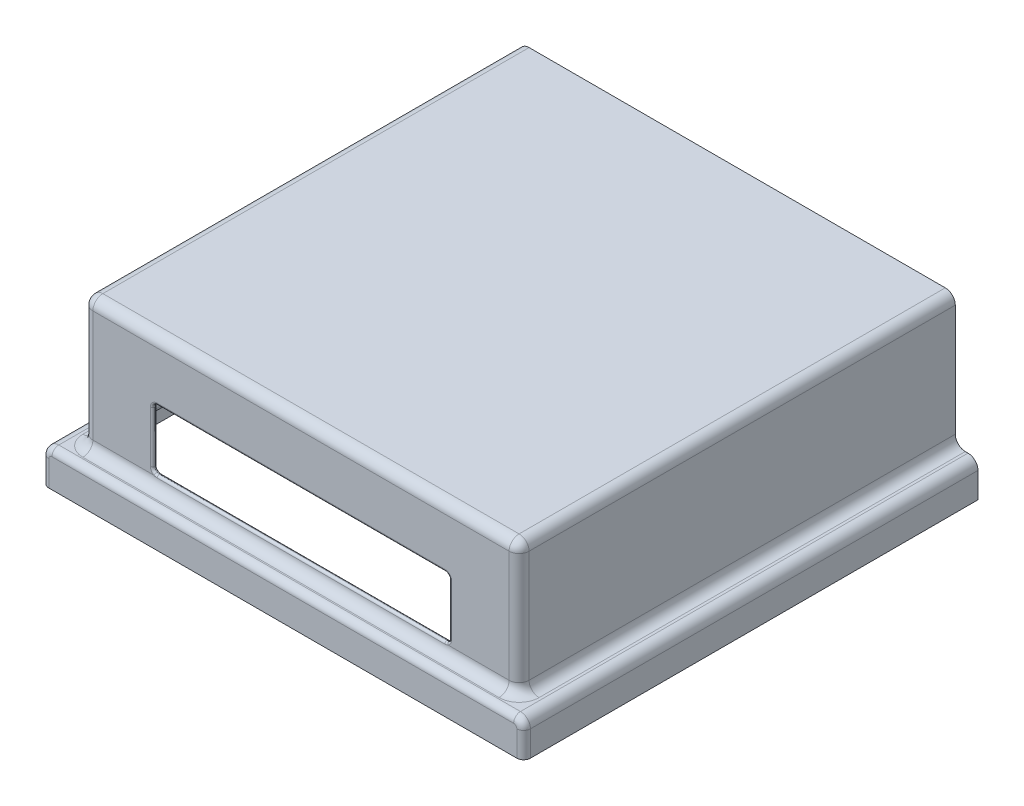
SolidWorks part; units mm, degrees
ref_plane "Front Plane" through (0, 0, 0) normal (0, 0, 1) x (1, 0, 0)
ref_plane "Top Plane" through (0, 0, 0) normal (0, 1, 0) x (1, 0, 0)
ref_plane "Right Plane" through (0, 0, 0) normal (1, 0, 0) x (0, 0, -1)
sketch "Sketch1" plane through (0, 0, 0) normal (0, 1, 0) x (1, 0, 0)
  line L1 (-121.92, -120.65) -> (121.92, -120.65)
  line L2 (-121.92, -120.65) -> (-121.92, 120.65)
  line L3 (-121.92, 120.65) -> (121.92, 120.65)
  line L4 (121.92, -120.65) -> (121.92, 120.65)
  line L5 (-121.92, -120.65) -> (121.92, 120.65) construction
  line L6 (-121.92, 120.65) -> (121.92, -120.65) construction
  point P0 (0, 0)
  dimension "D1" = 243.84
  dimension "D2" = 241.3
extrude "Boss-Extrude1" add sketch "Sketch1" along normal blind 2.54
sketch "Sketch2" plane through (121.92, 0, 0) normal (1, 0, 0) x (0, 0, -1)
  line L1 (-120.65, 0) -> (120.65, 0) construction
  line L2 (-120.65, -73.66) -> (120.65, -73.66)
  line L3 (-120.65, -73.66) -> (-120.65, 2.54)
  line L4 (-120.65, 2.54) -> (120.65, 2.54)
  line L5 (120.65, -73.66) -> (120.65, 2.54)
  line L6 (-120.65, -73.66) -> (120.65, 2.54) construction
  line L7 (-120.65, 2.54) -> (120.65, -73.66) construction
  line L10 (-120.65, 2.54) -> (120.65, 2.54) construction
  point P0 (0, 0)
  dimension "D1" = 241.3
  dimension "D2" = 76.2
  dimension "D3" = 0
extrude "Boss-Extrude2" add sketch "Sketch2" against normal blind 2.54
ref_plane "Plane1" through (0, 0, 0) normal (-1, 0, 0) x (0, 0, 1)
sketch "Sketch3" plane through (0, 0, 120.65) normal (0, 0, 1) x (1, 0, 0)
  line L1 (-121.92, 2.54) -> (121.92, 2.54)
  line L2 (-121.92, 2.54) -> (-121.92, -73.66)
  line L3 (-121.92, -73.66) -> (121.92, -73.66)
  line L4 (121.92, 2.54) -> (121.92, -73.66)
  line L5 (-121.92, 2.54) -> (121.92, -73.66) construction
  line L6 (-121.92, -73.66) -> (121.92, 2.54) construction
  line L10 (-121.92, 2.54) -> (121.92, 2.54) construction
  point P0 (0, 2.54)
  dimension "D1" = 243.84
  dimension "D2" = 76.2
  dimension "D3" = 0
extrude "Boss-Extrude3" add sketch "Sketch3" along normal blind 2.54
sketch "Sketch6" plane through (0, 0, 123.19) normal (0, 0, 1) x (1, 0, 0)
  line L0 (121.92, -73.66) -> (121.92, 2.54) construction
  line L1 (-82.931, -64.77) -> (82.931, -64.77)
  line L2 (-82.931, -64.77) -> (-82.931, -30.988)
  line L3 (-82.931, -30.988) -> (82.931, -30.988)
  line L4 (82.931, -64.77) -> (82.931, -30.988)
  line L5 (-82.931, -64.77) -> (82.931, -30.988) construction
  line L6 (-82.931, -30.988) -> (82.931, -64.77) construction
  line L7 (121.92, 2.54) -> (-121.92, 2.54) construction
  point P0 (0, -47.879)
  dimension "D1" = 165.862
  dimension "D2" = 121.92
  dimension "D3" = 33.528
  dimension "D4" = 33.782
extrude "Cut-Extrude3" cut sketch "Sketch6" against normal blind 2.54
ref_plane "Plane2" through (0, 0, -28.702) normal (0, 0, -1) x (-1, 0, 0)
ref_plane "Plane3" through (0, 0, 47.498) normal (0, 0, 1) x (1, 0, 0)
ref_plane "Plane4" through (0, 0, 9.398) normal (0, 0, 1) x (1, 0, 0)
ref_plane "Plane6" through (0, -71.12, 0) normal (0, -1, 0) x (-1, 0, 0)
sketch "Sketch22" plane through (0, -71.12, 0) normal (0, -1, 0) x (-1, 0, 0)
  line L0 (-119.38, 120.65) -> (-121.92, 120.65) construction
  line L1 (-121.92, -123.19) -> (-134.62, -123.19)
  line L2 (-121.92, -123.19) -> (-121.92, 120.65)
  line L3 (-121.92, 120.65) -> (-134.62, 120.65)
  line L4 (-134.62, -123.19) -> (-134.62, 120.65)
  line L5 (-121.92, -123.19) -> (-121.92, 120.65) construction
  dimension "D1" = 243.84
  dimension "D2" = 0
  dimension "D3" = 12.7
  dimension "D4" = 0
extrude "Boss-Extrude8" add sketch "Sketch22" along normal blind 2.54 separate body
ref_plane "Plane7" through (121.92, 0, 0) normal (1, 0, 0) x (0, 0, -1)
sketch "Sketch24" plane through (0, -71.12, 0) normal (0, 1, 0) x (1, 0, 0)
  line L0 (121.92, 120.65) -> (134.62, 120.65) construction
  line L1 (134.62, -123.19) -> (131.572, -123.19)
  line L2 (134.62, -123.19) -> (134.62, 120.65)
  line L3 (134.62, 120.65) -> (131.572, 120.65)
  line L4 (131.572, -123.19) -> (131.572, 120.65)
  dimension "D1" = 3.048
extrude "Boss-Extrude10" add sketch "Sketch24" against normal blind 19.812
mirror "Mirror15" about plane through (0, 0, 0) normal (-1, 0, 0) of "Boss-Extrude2"
mirror "Mirror18" about plane through (0, 0, 0) normal (-1, 0, 0) of "Boss-Extrude8", "Boss-Extrude10"
ref_plane "Plane8" through (0, 0, 120.65) normal (0, 0, 1) x (1, 0, 0)
sketch "Sketch27" plane through (0, 0, 120.65) normal (0, 0, 1) x (1, 0, 0)
  line L1 (-134.62, -71.12) -> (134.62, -71.12)
  line L2 (-134.62, -71.12) -> (-134.62, -90.932)
  line L3 (-134.62, -90.932) -> (134.62, -90.932)
  line L4 (134.62, -71.12) -> (134.62, -90.932)
extrude "Boss-Extrude11" add sketch "Sketch27" along normal blind 12.7
ref_plane "Plane9" through (0, 0, 120.65) normal (0, 0, -1) x (-1, 0, 0)
sketch "Sketch28" plane through (0, 0, 120.65) normal (0, 0, -1) x (-1, 0, 0)
  line L1 (-131.572, -73.66) -> (131.572, -73.66)
  line L2 (-131.572, -73.66) -> (-131.572, -90.932)
  line L3 (-131.572, -90.932) -> (131.572, -90.932)
  line L4 (131.572, -73.66) -> (131.572, -90.932)
extrude "Cut-Extrude6" cut sketch "Sketch28" against normal blind 9.652
sketch "Sketch29" [suppressed] plane through (0, 0, 133.35) normal (0, 0, 1) x (1, 0, 0)
  line L0 (-134.62, -71.12) -> (-134.62, -90.932) construction
  line L1 (134.62, -90.932) -> (134.62, -71.12) construction
  circle A0 centre (-115.57, -81.026) radius 1.397
  circle A1 centre (115.57, -81.026) radius 1.397
  point P0 (-134.62, -81.026)
  dimension "D1" = 2.794
  dimension "D2" = 2.794
  dimension "D3" = 19.05
  dimension "D4" = 19.05
extrude "Cut-Extrude7" [suppressed] cut sketch "Sketch29" against normal blind 9.652
fillet "Fillet4" radius 5.588 11 edges at (-134.62, -71.12, 6.35) (134.62, -71.12, 6.35) (0, -73.66, 130.302) (121.92, -71.12, 1.27) (121.92, -34.29, 123.19) (121.92, 2.54, 1.27) (0, 2.54, 123.19) (-121.92, 2.54, 1.27)
fillet "Fillet5" radius 2.54 14 edges at (-119.38, -73.66, 0) (131.572, -85.09, 130.302) (131.572, -75.2967, 128.6653) (-131.572, -85.09, 130.302) (-131.572, -75.2967, 128.6653) (-119.38, 0, 0) (119.38, 0, 0) (131.572, -73.66, 2.032) (-131.572, -73.66, 2.032) (-119.38, -36.83, 120.65)
fillet "Fillet6" radius 3.81 5 edges at (134.62, -83.82, 133.35) (132.9833, -72.7567, 133.35) (0, -71.12, 133.35) (-132.9833, -72.7567, 133.35) (-134.62, -83.82, 133.35)
fillet "Fillet7" radius 2.54 4 edges at (82.931, -64.77, 121.92) (82.931, -30.988, 121.92) (-82.931, -64.77, 121.92) (-82.931, -30.988, 121.92)
fillet "Fillet8" radius 1.27 16 edges at (-82.1871, -31.7319, 120.65) (0, -30.988, 120.65) (82.1871, -31.7319, 120.65) (82.931, -47.879, 120.65) (82.1871, -64.0261, 120.65) (0, -64.77, 120.65) (-82.1871, -64.0261, 120.65) (-82.1871, -31.7319, 123.19) (0, -30.988, 123.19) (82.1871, -31.7319, 123.19) (82.931, -47.879, 123.19) (82.1871, -64.0261, 123.19) (0, -64.77, 123.19) (-82.1871, -64.0261, 123.19) (-82.931, -47.879, 120.65) (-82.931, -47.879, 123.19)
scale "Scale1" [suppressed]
ref_plane "Plane10" through (0, -90.932, 0) normal (0, -1, 0) x (-1, 0, 0)
